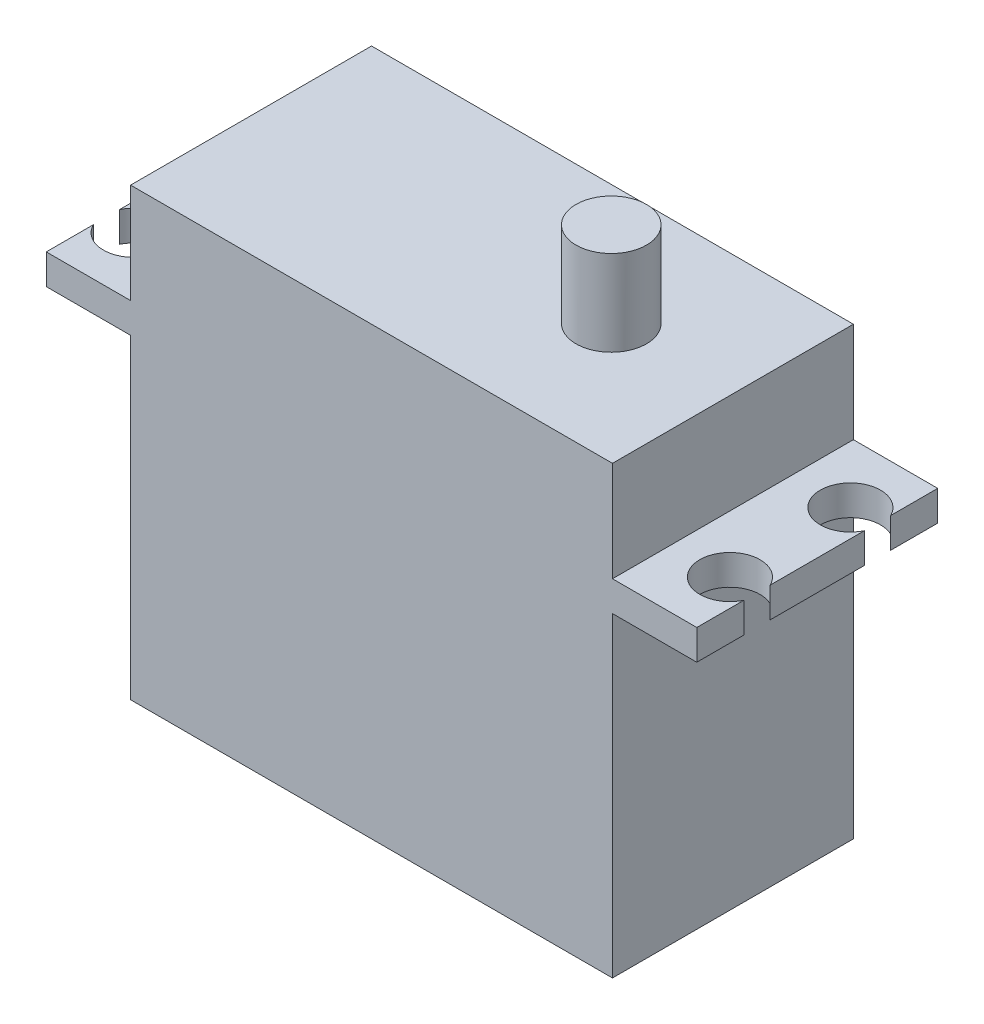
SolidWorks part; units mm, degrees
ref_plane "Front Plane" through (0, 0, 0) normal (0, 0, 1) x (1, 0, 0)
ref_plane "Top Plane" through (0, 0, 0) normal (0, 1, 0) x (1, 0, 0)
ref_plane "Right Plane" through (0, 0, 0) normal (1, 0, 0) x (0, 0, -1)
sketch "Sketch2" plane through (0, 0, 0) normal (0, 1, 0) x (1, 0, 0)
  line L1 (0, 0) -> (40, 0)
  line L2 (0, 0) -> (0, 20)
  line L3 (0, 20) -> (40, 20)
  line L4 (40, 0) -> (40, 20)
  dimension "D1" = 20
  dimension "D2" = 40
extrude "Boss-Extrude1" add sketch "Sketch2" along normal blind 37
sketch "Sketch3" plane through (0, 0, 0) normal (-1, 0, 0) x (0, 0, 1)
  line L0 (-20, 28.7) -> (0, 28.7)
  line L1 (-20, 37) -> (-20, 0) construction
  line L2 (0, 37) -> (0, 0) construction
  line L3 (0, 28.7) -> (0, 26.2)
  line L4 (0, 26.2) -> (-20, 26.2)
  line L5 (-20, 26.2) -> (-20, 28.7)
  line L6 (-20, 0) -> (0, 0) construction
  dimension "D1" = 28.7
  dimension "D2" = 2.5
extrude "Boss-Extrude2" add sketch "Sketch3" along normal blind 7
ref_plane "Plane1" through (20, 0, 0) normal (-1, 0, 0) x (0, 0, 1)
mirror "Mirror1" about plane through (20, 0, 0) normal (-1, 0, 0) of "Boss-Extrude2"
sketch "Sketch4" plane through (0, 28.7, 0) normal (0, 1, 0) x (1, 0, 0)
  line L0 (-7, 10) -> (47, 10) construction
  line L1 (-7, 0) -> (-7, 20) construction
  line L2 (47, 0) -> (47, 20) construction
  line L3 (20, 20) -> (20, 0) construction
  line L4 (40, 20) -> (0, 20) construction
  line L6 (0, 0) -> (40, 0) construction
  circle A0 centre (-4.75, 15) radius 2.5
  circle A1 centre (-4.75, 5) radius 2.5
  circle A2 centre (44.75, 5) radius 2.5
  circle A3 centre (44.75, 15) radius 2.5
  point P14 (0, 0)
  dimension "D1" = 5
  dimension "D2" = 10
  dimension "D3" = 49.5
extrude "Cut-Extrude5" cut sketch "Sketch4" against normal blind 7.25
sketch "Sketch5" plane through (0, 37, 0) normal (0, 1, 0) x (1, 0, 0)
  line L0 (0, 10) -> (40, 10) construction
  line L1 (0, 20) -> (0, 0) construction
  line L2 (40, 0) -> (40, 20) construction
  circle A0 centre (29.9, 10) radius 2.925
  dimension "D2" = 5.85
  dimension "D1" = 29.9
extrude "Boss-Extrude4" add sketch "Sketch5" along normal blind 7.1
